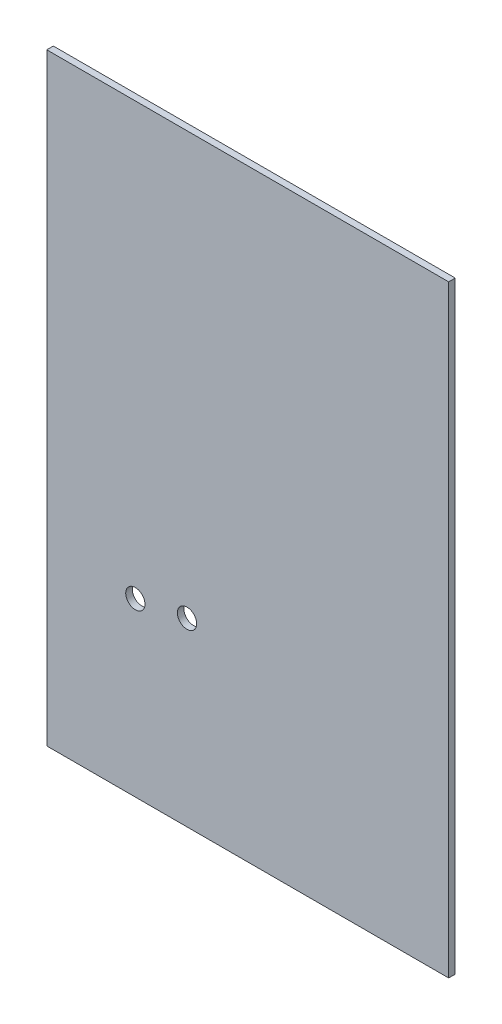
SolidWorks part; units mm, degrees
material "Polypropylene"
ref_plane "Front Plane" through (0, 0, 0) normal (0, 0, 1) x (1, 0, 0)
ref_plane "Top Plane" through (0, 0, 0) normal (0, 1, 0) x (1, 0, 0)
ref_plane "Right Plane" through (0, 0, 0) normal (1, 0, 0) x (0, 0, -1)
sketch "Sketch1" plane through (0, 0, 0) normal (0, 0, 1) x (1, 0, 0)
  line L1 (0, 0) -> (292.1, 0)
  line L2 (0, 0) -> (0, -438.15)
  line L3 (0, -438.15) -> (292.1, -438.15)
  line L4 (292.1, 0) -> (292.1, -438.15)
  circle A0 centre (64.3744, -313.2564) radius 7
  circle A1 centre (101.9257, -306.8134) radius 7
  circle A2 centre (101.9257, -306.8134) radius 7 construction
  circle A3 centre (64.3744, -313.2564) radius 7 construction
  dimension "D1" = 438.15
  dimension "D2" = 292.1
extrude "Boss-Extrude1" add sketch "Sketch1" along normal blind 4.7625
